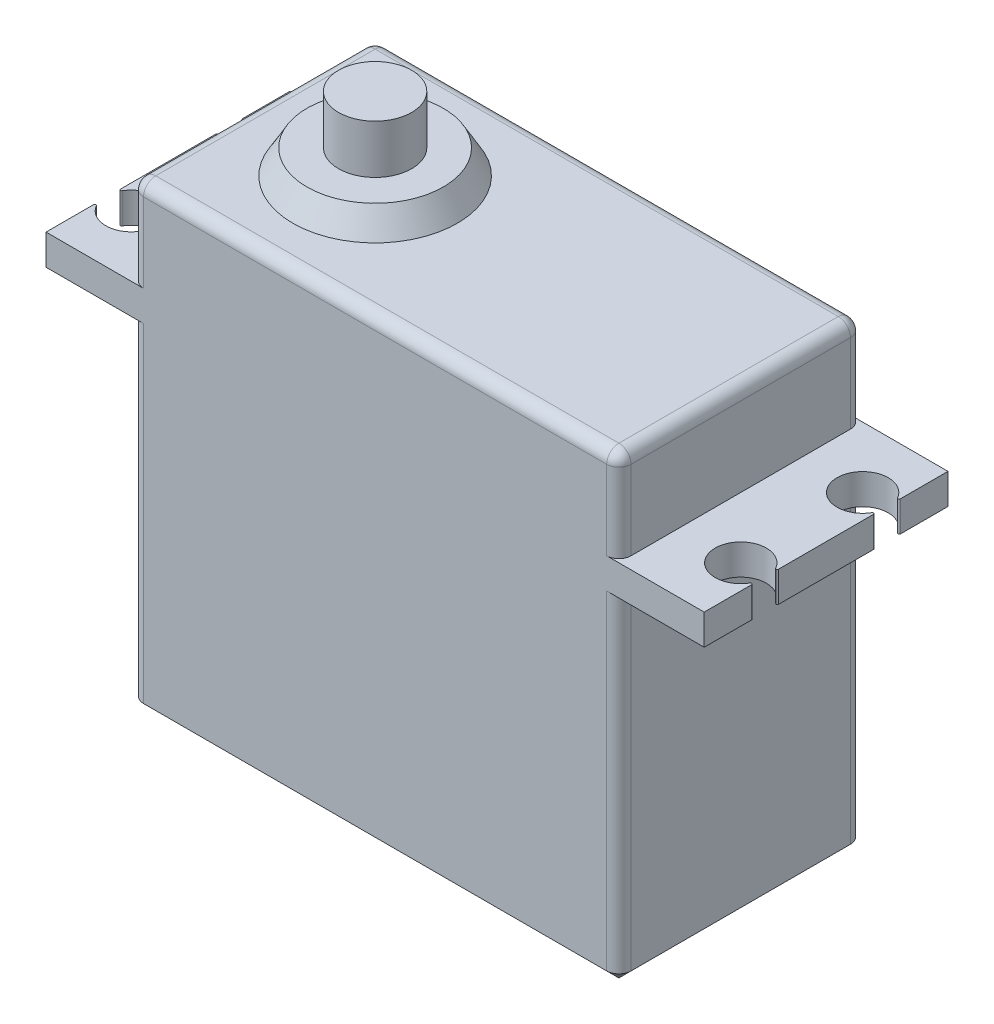
SolidWorks part; units mm, degrees
material "ABS"
ref_plane "Front Plane" through (0, 0, 0) normal (0, 0, 1) x (1, 0, 0)
ref_plane "Top Plane" through (0, 0, 0) normal (0, 1, 0) x (1, 0, 0)
ref_plane "Right Plane" through (0, 0, 0) normal (1, 0, 0) x (0, 0, -1)
sketch "Sketch1" plane through (0, 0, 0) normal (0, 1, 0) x (1, 0, 0)
  line L1 (0, 0) -> (40, 0)
  line L2 (0, 0) -> (0, 20)
  line L3 (0, 20) -> (40, 20)
  line L4 (40, 0) -> (40, 20)
  dimension "D1" = 40
  dimension "D2" = 20
extrude "Boss-Extrude1" add sketch "Sketch1" along normal blind 28
sketch "Sketch2" plane through (0, 28, 0) normal (0, 1, 0) x (1, 0, 0)
  line L0 (0, 0) -> (40, 0) construction
  line L1 (47, 20) -> (-7, 20)
  line L2 (47, 20) -> (47, 0)
  line L3 (47, 0) -> (-7, 0)
  line L4 (-7, 20) -> (-7, 0)
  line L5 (0, 20) -> (0, 0) construction
  line L8 (20, 20) -> (20, 0) construction
  line L9 (0, 20) -> (40, 20) construction
  dimension "D1" = 7
extrude "Boss-Extrude2" add sketch "Sketch2" along normal blind 2.5
sketch "Sketch3" plane through (0, 30.5, 0) normal (0, 1, 0) x (1, 0, 0)
  line L0 (47, 20) -> (-7, 20) construction
  line L1 (0, 20) -> (40, 20)
  line L2 (0, 20) -> (0, 0)
  line L3 (0, 0) -> (40, 0)
  line L4 (40, 20) -> (40, 0)
  line L5 (-7, 0) -> (47, 0) construction
  line L6 (40, 0) -> (40, 20) construction
  line L7 (0, 20) -> (0, 0) construction
extrude "Boss-Extrude3" add sketch "Sketch3" along normal blind 7.5
sketch "Sketch4" plane through (0, 38, 0) normal (0, 1, 0) x (1, 0, 0)
  line L0 (0, 10) -> (10, 10) construction
  line L1 (0, 20) -> (0, 0) construction
  circle A0 centre (10, 10) radius 6.75
  dimension "D1" = 13.5
  dimension "D2" = 10
extrude "Boss-Extrude4" add sketch "Sketch4" along normal blind 2
sketch "Sketch5" plane through (0, 40, 0) normal (0, 1, 0) x (1, 0, 0)
  circle A0 centre (10, 10) radius 3
  dimension "D1" = 6
extrude "Boss-Extrude5" add sketch "Sketch5" along normal blind 4
fillet "Fillet1" radius 1 12 edges at (20, 38, -20) (40, 38, -10) (0, 38, -10) (20, 38, 0)
chamfer "Chamfer1" distance 1 angle 45 8 edges at (20, 0, 0) (0, 0, -10) (40, 0, -10) (39.7071, 0, -0.2929) (0.2929, 0, -0.2929) (39.7071, 0, -19.7071) (0.2929, 0, -19.7071) (20, 0, -20)
chamfer "Chamfer2" distance 2 angle 30 1 edges at (10, 40, -3.25) first distance on face at (10, 40, -3.25)
ref_plane "Plane1" through (10, 0, 0) normal (1, 0, 0) x (0, 0, -1)
ref_plane "Plane2" through (0, 0, -10) normal (0, 0, 1) x (1, 0, 0)
ref_axis "Axis1" through (10, 46.2, -10) along (0, -1, 0)
sketch "Sketch6" plane through (0, 30.5, 0) normal (0, 1, 0) x (1, 0, 0)
  line L0 (0, 10) -> (-5, 10) construction
  line L1 (0, 19) -> (0, 1) construction
  line L2 (-5, 15) -> (-5, 5) construction
  circle A0 centre (-5, 5) radius 2.1
  circle A1 centre (-5, 15) radius 2.1
  dimension "D3" = 4.2
  dimension "D1" = 10
  dimension "D2" = 5
extrude "Cut-Extrude1" cut sketch "Sketch6" against normal through all
ref_plane "Plane3" through (20, 0, 0) normal (-1, 0, 0) x (0, 0, 1)
mirror "Mirror2" about plane through (20, 0, 0) normal (-1, 0, 0) of "Cut-Extrude1"
fillet "Fillet2" radius 0.1 8 edges at (-7, 29.25, -15.6403) (-7, 29.25, -14.3597) (-7, 29.25, -5.6403) (-7, 29.25, -4.3597) (47, 29.25, -4.3597) (47, 29.25, -14.3597) (47, 29.25, -5.6403) (47, 29.25, -15.6403)
